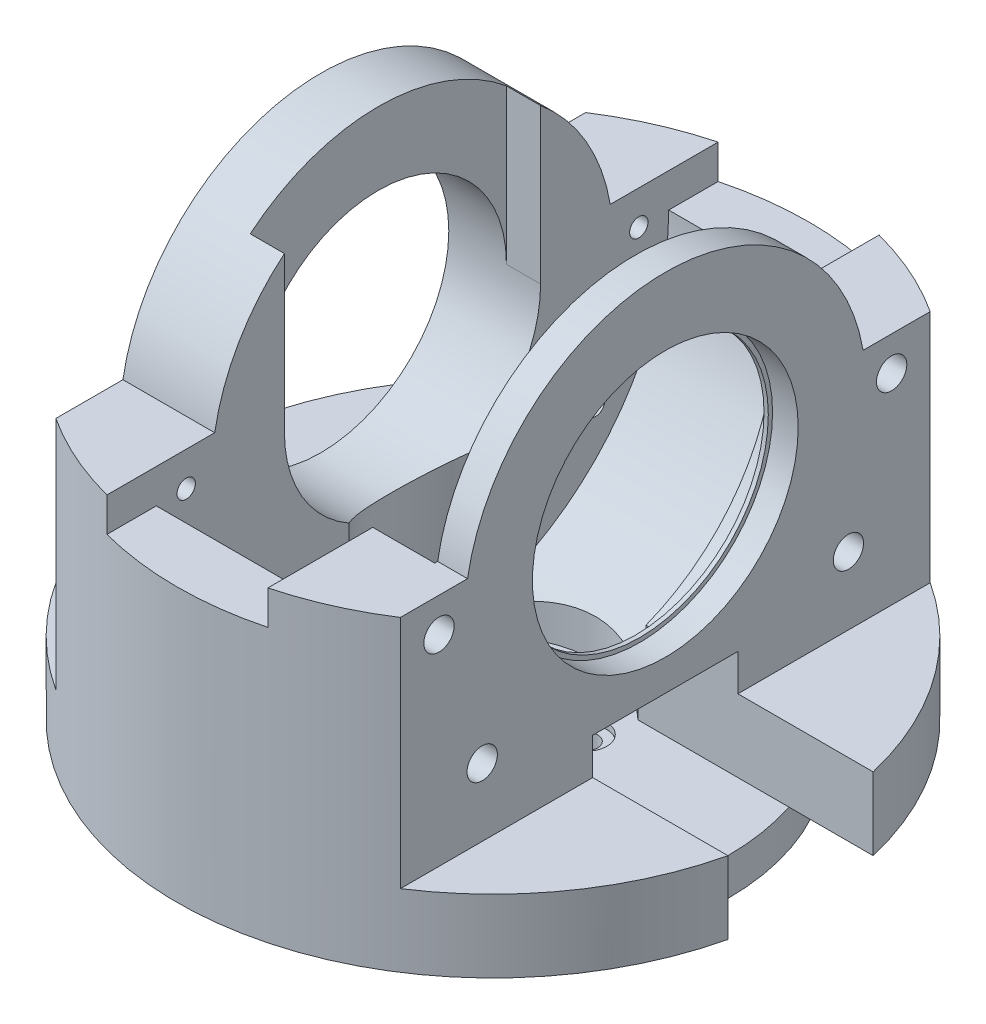
SolidWorks part; units mm, degrees
ref_plane "前视基准面" through (0, 0, 0) normal (0, 0, 1) x (1, 0, 0)
ref_plane "上视基准面" through (0, 0, 0) normal (0, 1, 0) x (1, 0, 0)
ref_plane "右视基准面" through (0, 0, 0) normal (1, 0, 0) x (0, 0, -1)
sketch "草图1" plane through (0, 0, 0) normal (0, 1, 0) x (1, 0, 0)
  circle A0 centre (0, 0) radius 56
  circle A1 centre (0, 0) radius 10
extrude "凸台-拉伸1" add sketch "草图1" along normal blind 5
sketch "草图2" plane through (0, 0, 0) normal (0, -1, 0) x (1, 0, 0)
  circle A0 centre (0, 0) radius 56
  circle A1 centre (0, 0) radius 45
extrude "凸台-拉伸2" add sketch "草图2" along normal blind 5.7
sketch "草图3" plane through (0, 5, 0) normal (0, 1, 0) x (1, 0, 0)
  line L0 (-13.8564, 8) -> (13.8564, -8) construction
  line L1 (13.8564, 8) -> (-13.8564, -8) construction
  line L2 (0, 16) -> (0, -16) construction
  circle A0 centre (0, 0) radius 16 construction
  arc A1 (0, 16) -> (13.8564, 8) centre (0, 0) cw construction
  point P5 (13.8564, -8)
  point P6 (0, 16)
  point P7 (13.8564, 8)
  point P8 (13.8564, 8)
  point P9 (0, -16)
  point P10 (-13.8564, -8)
  point P11 (-13.8564, 8)
hole_wizard "M5 六角圆柱头螺钉的柱形沉头孔1" positions "草图3" profile "草图4" counterbore size "M5" standard "GB" end condition through all
sketch "草图4" plane through (-13.8564, 5, -8) normal (1, 0, 0) x (0, 0, 1)
  line L0 (0, 0) -> (0, 10.7)
  line L1 (0, 10.7) -> (2.65, 10.7)
  line L3 (2.65, 10.7) -> (2.65, 1.4)
  line L4 (2.65, 1.4) -> (4.8, 1.4)
  line L5 (4.8, 1.4) -> (4.8, 0)
  line L7 (4.8, 0) -> (0, 0)
  line L11 (0, -6.35) -> (0, 107.95) construction
  dimension "通孔孔直径" = 5.3
  dimension "通孔孔深度" = 10.7
  dimension "柱形沉头孔直径" = 9.6
  dimension "柱形沉头孔深度" = 1.4
sketch "草图5" plane through (0, 5, 0) normal (0, 1, 0) x (1, 0, 0)
  circle A0 centre (0, 0) radius 74
  circle A1 centre (0, 0) radius 24
extrude "凸台-拉伸3" add sketch "草图5" along normal blind 4
sketch "草图7" plane through (0, 9, 0) normal (0, 1, 0) x (1, 0, 0)
  circle A0 centre (0, 0) radius 24
  circle A1 centre (0, 0) radius 74
extrude "凸台-拉伸4" add sketch "草图7" along normal blind 120
sketch "草图8" plane through (0, 0, 0) normal (1, 0, 0) x (0, 0, -1)
  line L0 (46.3141, 77) -> (74, 77)
  line L1 (74, 5) -> (74, 129) construction
  line L4 (-74, 129) -> (74, 9) construction
  line L8 (-74, 77) -> (-74, 129)
  line L9 (-74, 129) -> (74, 129)
  line L10 (74, 129) -> (74, 77)
  line L12 (-60.5, 77) -> (-74, 77)
  line L13 (-60.5, 77) -> (-46.3141, 77)
  arc A0 (-46.3141, 77) -> (46.3141, 77) centre (0, 69) cw
extrude "切除-拉伸1" cut sketch "草图8" along normal through all both and the other way through all
sketch "草图14" plane through (0, 0, 0) normal (1, 0, 0) x (0, 0, -1)
  line L1 (74, 5) -> (74, 77) construction
  line L2 (74, 9) -> (0, 9) construction
  arc A1 (0, 9) -> (0, 129) centre (0, 69) ccw
  arc A2 (0, 129) -> (0, 9) centre (0, 69) ccw
  point P0 (37, 9)
extrude "切除-拉伸2" cut sketch "草图14" against normal blind 18.85 and the other way blind 18.85
sketch "草图15" plane through (0, 0, 0) normal (1, 0, 0) x (0, 0, -1)
  line L0 (-47, 69) -> (-47, 77)
  line L1 (-74, 77) -> (-74, 5) construction
  line L2 (-74, 9) -> (74, 9) construction
  line L3 (74, 5) -> (74, 77) construction
  line L4 (-59.4643, 77) -> (-46.3141, 77) construction
  line L6 (47, 69) -> (47, 77)
  line L7 (46.3141, 77) -> (59.4643, 77) construction
  line L10 (-47, 77) -> (-47, 117.7352)
  line L11 (-47, 117.7352) -> (47, 117.7352)
  line L12 (47, 77) -> (47, 117.7352)
  arc A0 (-47, 69) -> (47, 69) centre (0, 69) ccw
  dimension "D1" = 8
extrude "切除-拉伸3" cut sketch "草图15" along normal blind 14.5 from offset 18.85
sketch "草图16" plane through (-18.85, 0, 0) normal (1, 0, 0) x (0, 0, -1)
  line L2 (-30, 69) -> (-30, 118.0849)
  line L3 (-30, 118.0849) -> (30, 118.0849)
  line L4 (30, 69) -> (30, 118.0849)
  arc A0 (-46.3141, 77) -> (46.3141, 77) centre (0, 69) ccw construction
  arc A1 (-30, 69) -> (30, 69) centre (0, 69) ccw
extrude "切除-拉伸4" cut sketch "草图16" against normal blind 8
sketch "草图18" plane through (-26.85, 0, 0) normal (1, 0, 0) x (0, 0, -1)
  arc A0 (-46.3141, 77) -> (46.3141, 77) centre (0, 69) ccw construction
  circle A1 centre (0, 69) radius 47
extrude "切除-拉伸5" cut sketch "草图18" against normal through all from offset 20 offset against normal yes
sketch "草图27" plane through (33.35, 0, 0) normal (-1, 0, 0) x (0, 0, 1)
  line L0 (0, 22) -> (0, 5) construction
  line L1 (-56, 5) -> (56, 5) construction
  line L2 (0, 22) -> (17, 22) construction
  line L3 (17, 22) -> (17, 25.1822)
  line L4 (17, 25.1822) -> (-17, 25.1822)
  line L6 (-17, 25.1822) -> (-17, 11.6422)
  line L8 (17, 11.4067) -> (17, 22)
  line L9 (-17, 11.6422) -> (-17, 5)
  line L10 (-17, 5) -> (17, 5)
  line L11 (17, 5) -> (17, 11.4067)
  arc A0 (-46.3141, 77) -> (46.3141, 77) centre (0, 69) ccw construction
extrude "切除-拉伸13" cut sketch "草图27" along normal up to next and the other way through all
sketch "草图30" plane through (-46.85, 0, 0) normal (-1, 0, 0) x (0, 0, 1)
  circle A0 centre (0, 69) radius 47 construction
  circle A1 centre (0, 69) radius 42
extrude "切除-拉伸14" cut sketch "草图30" against normal blind 8
sketch "草图31" plane through (33.35, 0, 0) normal (-1, 0, 0) x (0, 0, 1)
  circle A0 centre (0, 69) radius 42 construction
  circle A1 centre (0, 69) radius 47
extrude "切除-拉伸16" cut sketch "草图31" against normal up to next from offset 13.5 offset against normal yes
sketch "草图32" plane through (46.85, 0, 0) normal (1, 0, 0) x (0, 0, -1)
  circle A0 centre (0, 69) radius 42
extrude "切除-拉伸17" cut sketch "草图32" against normal blind 8
sketch "草图33" plane through (-38.85, 0, 0) normal (-1, 0, 0) x (0, 0, 1)
  circle A0 centre (0, 69) radius 30
extrude "切除-拉伸18" cut sketch "草图33" against normal up to next
sketch "草图34" plane through (0, 0, 0) normal (0, 0, 1) x (1, 0, 0)
  line L0 (-46.85, 116) -> (-46.85, 77) construction
  line L1 (57.7148, 77) -> (-57.7148, 77) construction
  line L2 (-18.85, 77) -> (-46.85, 77) construction
  line L3 (46.85, 116) -> (46.85, 77) construction
  line L4 (-46.85, 77) -> (-57.7148, 77)
  line L5 (-57.7148, 77) -> (-74, 22)
  line L6 (46.85, 77) -> (57.7148, 77)
  line L7 (57.7148, 77) -> (72.0208, 25.1822)
  arc A0 (-46.85, 77) -> (-74, 22) centre (-116.134, 77) cw
  arc A1 (46.85, 77) -> (72.0208, 25.1822) centre (112.7726, 77) ccw
extrude "切除-拉伸19" cut sketch "草图34" against normal through all and the other way through all
sketch "草图35" plane through (46.85, 0, 0) normal (1, 0, 0) x (0, 0, -1)
  line L0 (-17, 25.1822) -> (-17, 30.5943)
  line L1 (-17, 30.5943) -> (17, 30.5943)
  line L2 (17, 30.5943) -> (17, 25.1822)
  line L3 (17, 25.1822) -> (-17, 25.1822)
  circle A0 centre (0, 69) radius 42 construction
  circle A1 centre (0, 69) radius 42 construction
extrude "切除-拉伸20" cut sketch "草图35" against normal up to next
sketch "草图36" plane through (-46.85, 0, 0) normal (-1, 0, 0) x (0, 0, 1)
  line L0 (0, 69) -> (-53, 69) construction
  line L1 (0, 69) -> (53, 69) construction
  line L2 (53, 69) -> (42.8813, 69) construction
  line L3 (42.8813, 69) -> (42.8813, 37.8521) construction
  line L4 (42.8813, 37.8521) -> (-42.8813, 37.8521) construction
  circle A0 centre (0, 69) radius 53 construction
  point P5 (-53, 69)
  point P8 (53, 69)
  point P11 (-42.8813, 37.8521)
  point P16 (42.8813, 37.8521)
hole_wizard "M4 六角圆柱头螺钉的柱形沉头孔2" positions "草图36" profile "草图37" counterbore size "M4" standard "GB"
sketch "草图37" plane through (-46.85, 37.8521, 42.8813) normal (0, 1, 0) x (0, 0, 1)
  line L0 (0, 0) -> (0, 46.9919)
  line L1 (0, 46.9919) -> (2.15, 45.7)
  line L2 (2.15, 45.7) -> (2.15, 23)
  line L3 (2.15, 23) -> (3.55, 23)
  line L4 (3.55, 23) -> (3.55, 0)
  line L5 (3.55, 0) -> (0, 0)
  line L10 (0, 46.9919) -> (-2.15, 45.7) construction
  line L11 (0, -6.35) -> (0, 107.95) construction
  dimension "孔直径" = 4.3
  dimension "孔深度" = 45.7
  dimension "柱形沉头孔直径" = 7.1
  dimension "柱形沉头孔深度" = 23
  dimension "导头角度" = 118
sketch "草图38" plane through (-46.85, 0, 0) normal (-1, 0, 0) x (0, 0, 1)
  line L0 (-49, 69) -> (-53, 69) construction
  line L1 (-53, 69) -> (-53, 65) construction
  line L2 (-46.8798, 37.85) -> (-42.8798, 37.85) construction
  line L3 (-42.8798, 37.85) -> (-38.8798, 37.85) construction
  line L4 (0, 69) -> (53, 69) construction
  line L5 (38.8798, 37.85) -> (42.8798, 37.85) construction
  arc A1 (-45.107, 41.1726) -> (-40.4084, 34.7048) centre (0, 69) ccw construction
  circle A2 centre (-53, 69) radius 4
  circle A3 centre (-42.8798, 37.85) radius 4
  circle A4 centre (53, 69) radius 4
  circle A5 centre (42.8798, 37.85) radius 4
  arc A6 (40.4084, 34.7048) -> (52.8491, 72.9972) centre (0, 69) ccw construction
  arc A7 (-52.8491, 72.9972) -> (-52.8491, 65.0028) centre (0, 69) ccw construction
extrude "切除-拉伸23" cut sketch "草图38" along normal up to next
sketch "草图39" plane through (46.85, 0, 0) normal (1, 0, 0) x (0, 0, -1)
  line L0 (0, 69) -> (-53, 69) construction
  line L1 (0, 69) -> (53, 69) construction
  line L2 (53, 69) -> (53, 37.85) construction
  line L3 (53, 37.85) -> (42.8798, 37.85) construction
  line L4 (42.8798, 37.85) -> (-42.8798, 37.85) construction
  line L6 (53, 69) -> (53, 37.85) construction
  circle A0 centre (0, 69) radius 53 construction
  circle A1 centre (-53, 69) radius 4
  circle A2 centre (53, 69) radius 4
  circle A3 centre (42.8798, 37.85) radius 4
  circle A4 centre (-42.8798, 37.85) radius 4
extrude "切除-拉伸24" cut sketch "草图39" along normal up to next
sketch "草图40" plane through (46.85, 0, 0) normal (1, 0, 0) x (0, 0, -1)
  point P0 (-53, 69)
  point P1 (-42.8798, 37.85)
  point P3 (42.8798, 37.85)
  point P5 (53, 69)
hole_wizard "M4 六角圆柱头螺钉的柱形沉头孔3" positions "草图40" profile "草图41" counterbore size "M4" standard "GB"
sketch "草图41" plane through (46.85, 69, 53) normal (0, 1, 0) x (0, 0, -1)
  line L0 (0, 0) -> (0, 46.9919)
  line L1 (0, 46.9919) -> (2.15, 45.7)
  line L2 (2.15, 45.7) -> (2.15, 23)
  line L3 (2.15, 23) -> (3.55, 23)
  line L4 (3.55, 23) -> (3.55, 0)
  line L5 (3.55, 0) -> (0, 0)
  line L10 (0, 46.9919) -> (-2.15, 45.7) construction
  line L11 (0, -6.35) -> (0, 107.95) construction
  dimension "孔直径" = 4.3
  dimension "孔深度" = 45.7
  dimension "柱形沉头孔直径" = 7.1
  dimension "柱形沉头孔深度" = 23
  dimension "导头角度" = 118
sketch "草图42" plane through (0, -5.7, 0) normal (0, -1, 0) x (1, 0, 0)
  circle A0 centre (0, 0) radius 45
  circle A1 centre (0, 0) radius 56
extrude "切除-拉伸25" cut sketch "草图42" against normal blind 2 and the other way through all
sketch "草图43" plane through (38.85, 0, 0) normal (1, 0, 0) x (0, 0, -1)
  circle A0 centre (0, 69) radius 42.5
  dimension "D1" = 85
extrude "切除-拉伸26" cut sketch "草图43" along normal blind 12
sketch "草图44" plane through (-38.85, 0, 0) normal (-1, 0, 0) x (0, 0, 1)
  circle A0 centre (0, 69) radius 42.5
  dimension "D1" = 85
extrude "切除-拉伸27" cut sketch "草图44" along normal blind 12
sketch "草图45" plane through (46.85, 0, 0) normal (1, 0, 0) x (0, 0, -1)
  circle A0 centre (0, 69) radius 47
extrude "切除-拉伸28" cut sketch "草图45" against normal blind 6.5
sketch "草图46" plane through (0, -3.7, 0) normal (0, -1, 0) x (1, 0, 0)
  circle A0 centre (0, 0) radius 55
  circle A1 centre (0, 0) radius 56
extrude "切除-拉伸29" cut sketch "草图46" against normal up to surface (8.7 mm away) up to face at (-1.1555, 5, 0)
sketch "草图47" plane through (-46.85, 0, 0) normal (-1, 0, 0) x (0, 0, 1)
  circle A0 centre (0, 69) radius 47
extrude "切除-拉伸30" cut sketch "草图47" against normal blind 4
sketch "草图48" plane through (0, 0, 0) normal (0, 1, 0) x (1, 0, 0)
  line L0 (-46.85, 57.2807) -> (-46.85, -57.2807)
  line L1 (46.85, 57.2807) -> (46.85, -57.2807)
  arc A0 (-46.85, 57.2807) -> (-46.85, -57.2807) centre (0, 0) ccw
  arc A1 (46.85, -57.2807) -> (46.85, 57.2807) centre (0, 0) ccw
extrude "切除-拉伸31" cut sketch "草图48" against normal blind 55 from surface starting at face at (5.35, 77, 51.8412)
sketch "草图49" plane through (0, 0, 0) normal (0, 0, 1) x (1, 0, 0)
  line L0 (18.85, 69) -> (18.85, 77) construction
  line L1 (18.85, 69) -> (18.85, 77)
  line L3 (18.85, 69) -> (-18.85, 69)
  line L4 (-18.85, 77) -> (18.85, 77) construction
  line L5 (-18.85, 77) -> (18.85, 77)
  line L6 (-18.85, 69) -> (-18.85, 77)
extrude "切除-拉伸34" cut sketch "草图49" against normal blind 80 and the other way blind 80
sketch "草图50" plane through (38.85, 0, 0) normal (1, 0, 0) x (0, 0, -1)
  line L0 (17, 30.0481) -> (17, 30.5943)
  line L1 (17, 30.5943) -> (-17, 30.5943)
  line L2 (-17, 30.5943) -> (-17, 30.0481)
  arc A0 (17, 30.0481) -> (-17, 30.0481) centre (0, 69) ccw
extrude "凸台-拉伸5" add sketch "草图50" along normal up to surface (1.5 mm away) up to face at (40.35, 62.4077, 0)
sketch "草图51" plane through (40.35, 0, 0) normal (1, 0, 0) x (0, 0, -1)
  circle A0 centre (0, 69) radius 31.12
extrude "切除-拉伸35" cut sketch "草图51" against normal blind 6
sketch "草图53" plane through (0, 0, 0) normal (1, 0, 0) x (0, 0, -1)
  line L1 (-71.5589, 77) -> (71.5589, 77)
  line L2 (-71.5589, 77) -> (-71.5589, 69)
  line L4 (71.5589, 77) -> (71.5589, 69)
  line L5 (57.2807, 22) -> (71.5589, 22)
  line L6 (71.5589, 22) -> (71.5589, 69)
  line L8 (-57.2807, 22) -> (-71.5589, 22)
  line L9 (-71.5589, 22) -> (-71.5589, 69)
  line L10 (-57.2807, 22) -> (57.2807, 22)
extrude "切除-拉伸36" cut sketch "草图53" against normal up to surface (-40.35 mm away) from surface up to face at (40.35, 69, -31.12) starting at face at (46.85, 69, -56.55)
sketch "草图54" plane through (-38.85, 0, 0) normal (-1, 0, 0) x (0, 0, 1)
  circle A0 centre (0, 69) radius 30
  circle A1 centre (0, 69) radius 42.5
extrude "凸台-拉伸6" add sketch "草图54" along normal blind 1.5
sketch "草图55" plane through (0, 0, 0) normal (1, 0, 0) x (0, 0, -1)
  line L0 (-57.2807, 22) -> (-71.5589, 22)
  line L2 (71.5589, 77) -> (71.5589, 69)
  line L4 (-71.5589, 77) -> (-71.5589, 69)
  line L5 (-71.5589, 22) -> (-71.5589, 69)
  line L6 (57.2807, 22) -> (71.5589, 22)
  line L7 (71.5589, 22) -> (71.5589, 69)
  line L8 (57.2807, 22) -> (-57.2807, 22)
  line L11 (71.5589, 77) -> (71.5589, 116)
  line L12 (71.5589, 116) -> (0, 116)
  line L14 (0, 116) -> (-71.5589, 116)
  line L17 (-71.5589, 116) -> (-71.5589, 77)
  arc A0 (46.3141, 77) -> (-46.3141, 77) centre (0, 69) ccw construction
extrude "切除-拉伸37" cut sketch "草图55" along normal up to surface (-40.35 mm away) from surface up to face at (-40.35, 69, 42.5) starting at face at (-46.85, 69, -49.45)
sketch "草图56" plane through (0, 0, 0) normal (1, 0, 0) x (0, 0, -1)
  circle A0 centre (0, 69) radius 30.12
extrude "切除-拉伸38" cut sketch "草图56" along normal blind 11 from offset 30
